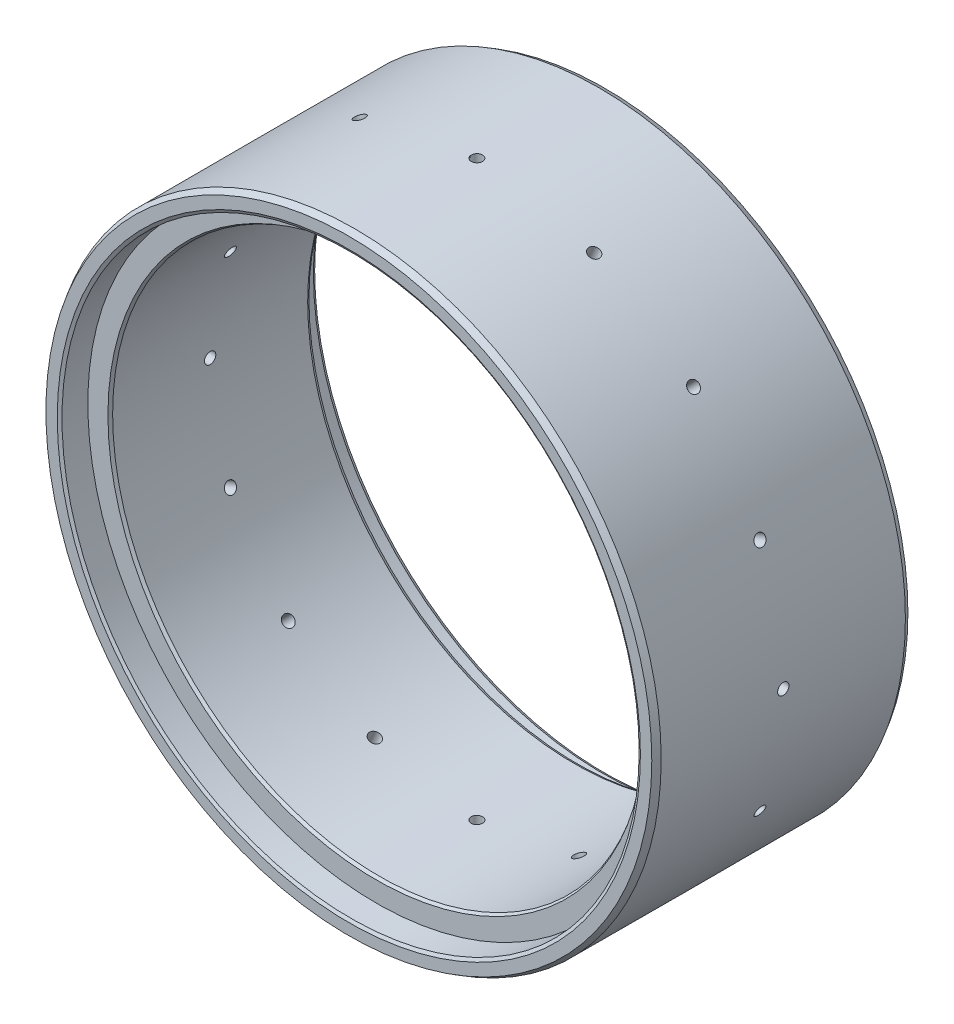
SolidWorks part; units mm, degrees
material "6061-T6 (SS)"
ref_plane "Front Plane" through (0, 0, 0) normal (0, 0, 1) x (1, 0, 0)
ref_plane "Top Plane" through (0, 0, 0) normal (0, 1, 0) x (1, 0, 0)
ref_plane "Right Plane" through (0, 0, 0) normal (1, 0, 0) x (0, 0, -1)
sketch "Sketch1" plane through (0, 0, 0) normal (0, 0, 1) x (1, 0, 0)
  circle A0 centre (0, 0) radius 67.7545
  circle A1 centre (0, 0) radius 58.9915
  dimension "D1" = 135.509
  dimension "D2" = 8.763
extrude "Extrude1" add sketch "Sketch1" along normal mid plane 56.642
sketch "Sketch11" plane through (0, 0, -28.321) normal (0, 0, -1) x (-1, 0, 0)
  circle A0 centre (0, 0) radius 63.8175
  dimension "D1" = 127.635
extrude "Extrude2" cut sketch "Sketch11" against normal blind 6.096
mirror "Mirror1" about plane through (0, 0, 0) normal (0, 0, 1) of "Extrude2"
sketch "Sketch2" plane through (0, 0, 0) normal (0, 0, 1) x (1, 0, 0)
  line L0 (0, 0) -> (0, 67.7545) construction
  line L1 (0, 0) -> (13.2182, 66.4526) construction
  circle A0 centre (0, 0) radius 67.7545 construction
  dimension "D1" = 11.25
ref_plane "Plane1" through (0, 67.7545, 0) normal (0, 1, 0) x (-1, 0, 0)
ref_plane "Plane2" through (13.2182, 66.4526, 0) normal (0.1951, 0.9808, 0) x (-0.9808, 0.1951, 0)
sketch "Sketch3" plane through (0, 67.7545, 0) normal (0, 1, 0) x (-1, 0, 0)
  line L0 (0, 0) -> (0, 28.321) construction
  line L1 (0, 28.321) -> (0, -28.321) construction
  line L2 (67.7545, 28.321) -> (-67.7545, 28.321) construction
  point P7 (0, 14.1605)
sketch "Sketch6" plane through (13.2182, 66.4526, 0) normal (0.1951, 0.9808, 0) x (-0.9808, 0.1951, 0)
  line L0 (0, 0) -> (0, 28.321) construction
  line L1 (67.7545, 28.321) -> (-67.7545, 28.321) construction
  point P5 (0, 14.1605)
hole_wizard "Tap Drill for M3x0.5 Tap1" positions "Sketch5" profile "Sketch4" hole size "M3x0.5" standard "Ansi Metric"
sketch "Sketch5" plane through (0, 67.7545, 0) normal (0, 1, 0) x (-1, 0, 0)
  point P6 (0, 0)
sketch "Sketch4" plane through (0, 67.7545, 0) normal (1, 0, 0) x (0, 0, 1)
  line L0 (0, 0) -> (0, 10.9111)
  line L1 (0, 10.9111) -> (1.25, 10.16)
  line L2 (1.25, 10.16) -> (1.25, 0)
  line L5 (1.25, 0) -> (0, 0)
  line L10 (0, 10.9111) -> (-1.25, 10.16) construction
  line L11 (0, -6.35) -> (0, 107.95) construction
  dimension "Hole Dia." = 2.5
  dimension "Hole Depth" = 10.16
  dimension "Drill Angle" = 118
pattern_circular "CirPattern1" count 16 over 360 about axis through (0, 0, 28.321) along (0, 0, -1) of "Tap Drill for M3x0.5 Tap1"
chamfer "Chamfer1" distance 0.381 angle 60 4 edges at (-58.9915, 0, -22.225) (-63.8175, 0, 28.321) (58.9915, 0, 22.225) (-63.8175, 0, -28.321) first distance on face at (-58.9915, 0, -22.225) first distance on face at (-63.8175, 0, 22.225) first distance on face at (58.9915, 0, 22.225) first distance on face at (-63.8175, 0, -28.321)
chamfer "Chamfer3" distance 0.762 angle 60 2 edges at (67.7545, 0, 28.321) (67.7545, 0, -28.321) first distance on face at (64.4774, 0, 28.321) first distance on face at (64.1985, 0, -28.321)
